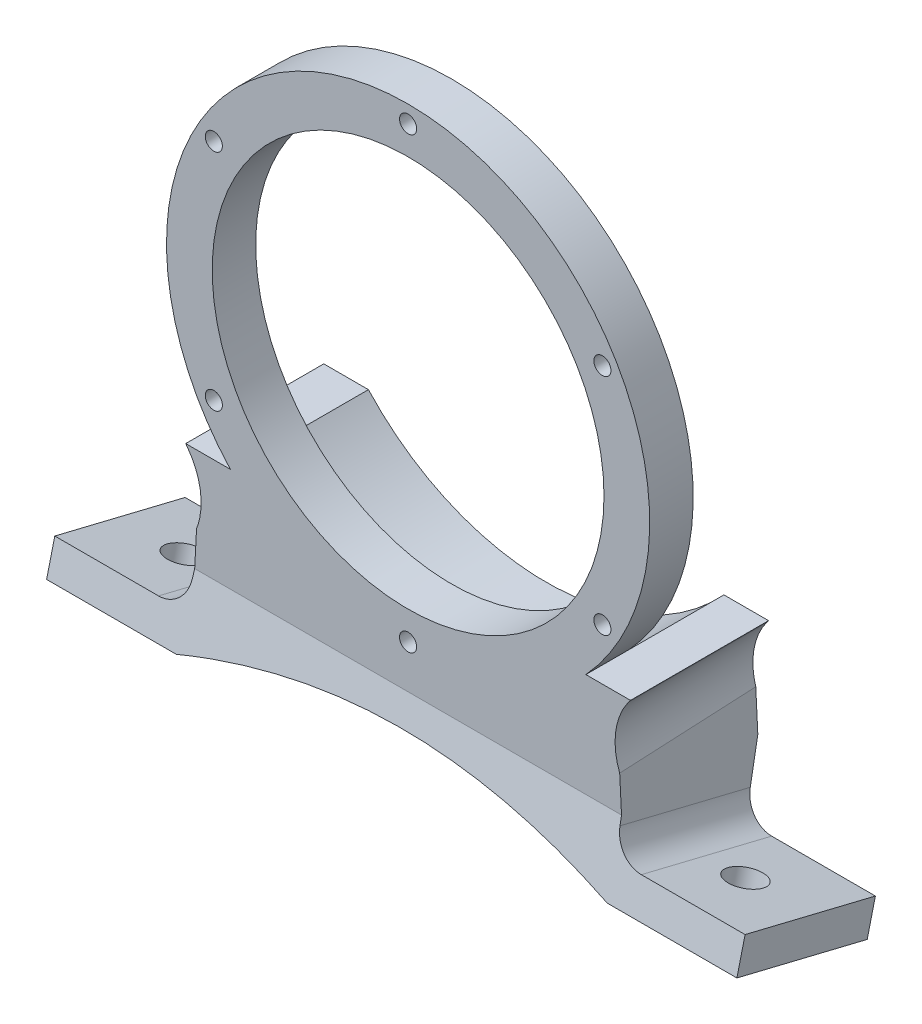
SolidWorks part; units mm, degrees
ref_plane "Front Plane" through (0, 0, 0) normal (0, 0, 1) x (1, 0, 0)
ref_plane "Top Plane" through (0, 0, 0) normal (0, 1, 0) x (1, 0, 0)
ref_plane "Right Plane" through (0, 0, 0) normal (1, 0, 0) x (0, 0, -1)
sketch "Sketch1" plane through (0, 0, 0) normal (0, 0, 1) x (1, 0, 0)
  circle A0 centre (0, 0) radius 44.45
  circle A1 centre (35.7452, -20.6375) radius 1.575
  circle A2 centre (0, 0) radius 44.45
  circle A3 centre (0, -41.275) radius 1.575
  circle A4 centre (0, 0) radius 44.45
  circle A5 centre (-35.7452, -20.6375) radius 1.575
  circle A6 centre (0, 0) radius 44.45
  circle A7 centre (-35.7452, 20.6375) radius 1.575
  circle A8 centre (0, 0) radius 44.45
  circle A9 centre (0, 41.275) radius 1.575
  circle A10 centre (0, 0) radius 44.45
  circle A11 centre (35.7452, 20.6375) radius 1.575
  circle A12 centre (0, 0) radius 36.0426
  point P24 (0, 0)
  dimension "D1" = 3.15
  dimension "D2" = 6
extrude "Boss-Extrude1" add sketch "Sketch1" along normal blind 8 contours A0 A12 A11 A9 A7 A5 A3 A1 region at (-43.1928, 0, 0)
sketch "Sketch4" plane through (0, 0, 8) normal (0, 0, 1) x (1, 0, 0)
  line L0 (-63.5, -44.45) -> (-39.6557, -44.45)
  line L1 (63.5, -44.45) -> (63.5, -49.2125)
  line L2 (63.5, -49.2125) -> (-63.5, -49.2125)
  line L3 (-63.5, -49.2125) -> (-63.5, -44.45)
  line L4 (-40.9153, -30.1094) -> (-32.699, -30.1094)
  line L5 (32.699, -30.1094) -> (40.9153, -30.1094)
  line L6 (39.6557, -44.45) -> (63.5, -44.45)
  line L7 (-36.0507, -35.7909) -> (-39.6557, -44.45)
  line L8 (36.0507, -35.7909) -> (39.6557, -44.45)
  circle A0 centre (0, 0) radius 44.45
  circle A1 centre (0, 0) radius 44.45 construction
  arc A2 (-40.9153, -30.1094) -> (-36.0507, -35.7909) centre (0, 0) ccw
  arc A3 (36.0507, -35.7909) -> (40.9153, -30.1094) centre (0, 0) ccw
  point P17 (24.5934, -44.45)
  circle M11 centre (0, 0) radius 44.45
  dimension "D2" = 127
  dimension "D3" = 6.35
  dimension "D1" = 4.7625
extrude "Boss-Extrude2" add sketch "Sketch4" against normal blind 25.4 contours A2 L7 L0 L3 L2 L1 L6 L8 A3 L5 L4 M11 region at (-51.5779, -45.7343, 8)
ref_plane "Plane1" through (0, -48.2929, 11.7725) normal (0, -0.9715, 0.2368) x (-1, 0, 0)
ref_axis "Axis1" through (0, 0, 8) along (0, 0, -1)
sketch "Sketch5" plane through (0, -48.2929, 11.7725) normal (0, -0.9715, 0.2368) x (-1, 0, 0)
  line L1 (-63.5, 28.5604) -> (63.5, 28.5604)
  line L2 (-63.5, 28.5604) -> (-63.5, 3.883)
  line L3 (-63.5, 3.883) -> (63.5, 3.883)
  line L4 (63.5, 28.5604) -> (63.5, 3.883)
extrude "Boss-Extrude3" add sketch "Sketch5" along normal blind 12.7 and the other way up to surface other way up to face at (0, -49.2125, -4.7)
sketch "Sketch6" plane through (0, -0.9196, -3.7725) normal (0, 0.2368, 0.9715) x (1, 0, 0)
  line L0 (63.5, -62.4071) -> (-63.5, -62.4071) construction
  line L1 (-39.6557, -62.4071) -> (-39.6557, -69.7981)
  line L2 (-39.6557, -69.7981) -> (39.6557, -69.7981)
  line L3 (39.6557, -69.7981) -> (39.6557, -62.4071)
  spline S0 degree 2 poles (-39.6557, -62.4071) (0, -47.6334) (39.6557, -62.4071) knots 0 0 0 1 1 1
  point P2 (-39.6557, -45.0801)
  point P4 (39.6557, -45.0801)
extrude "Cut-Extrude1" cut sketch "Sketch6" against normal through all
sketch "Sketch7" plane through (0, -60.6315, 14.7804) normal (0, -0.9715, 0.2368) x (1, 0, 0)
  line L0 (-63.5, -3.883) -> (-63.5, -28.5604) construction
  line L1 (-39.6557, -3.883) -> (-63.5, -3.883) construction
  line L2 (0, 0) -> (0, -35.7035) construction
  line L3 (0, 7.7724) -> (0, 0) construction
  circle A0 centre (-51.5779, -16.2217) radius 3.2639
  circle A1 centre (51.5779, -16.2217) radius 3.2639
  point P4 (-63.5, -16.2217)
  point P7 (-51.5779, -3.883)
  dimension "D1" = 6.5278
extrude "Cut-Extrude2" cut sketch "Sketch7" against normal through all
sketch "Sketch8" plane through (0, -6.7642, -27.7478) normal (0, -0.2368, -0.9715) x (-1, 0, 0)
  line L0 (-39.5977, -37.8778) -> (-39.5977, -56.0571)
  line L1 (-39.5977, -56.0571) -> (-63.5, -56.0571)
  line L3 (-63.5, -56.0571) -> (-63.5, -37.8778)
  line L4 (-63.5, -37.8778) -> (-39.5977, -37.8778)
  line L6 (-39.6557, -62.4071) -> (-63.5, -62.4071) construction
  line L7 (0, 0) -> (0, -27.5431) construction
  line L8 (0, -1.8947) -> (0, 0) construction
  line L9 (39.5977, -37.8778) -> (39.5977, -56.0571)
  line L10 (39.5977, -56.0571) -> (63.5, -56.0571)
  line L11 (63.5, -56.0571) -> (63.5, -37.8778)
  line L12 (63.5, -37.8778) -> (39.5977, -37.8778)
  dimension "D1" = 6.35
extrude "Cut-Extrude3" cut sketch "Sketch8" against normal through all
sketch "Sketch10" plane through (0, -6.7642, -27.7478) normal (0, -0.2368, -0.9715) x (-1, 0, 0)
  line L0 (-38.5619, -36.5118) -> (-39.5977, -56.0571)
  line L1 (-39.5977, -56.0571) -> (-58.3294, -36.5118)
  line L2 (-58.3294, -36.5118) -> (-38.5619, -36.5118)
  line L3 (0, 0) -> (0, -64.3842) construction
  line L4 (38.5619, -36.5118) -> (39.5977, -56.0571)
  line L5 (39.5977, -56.0571) -> (58.3294, -36.5118)
  line L6 (58.3294, -36.5118) -> (38.5619, -36.5118)
  line L7 (-36.0507, -30.6516) -> (-39.5977, -38.9289) construction
extrude "Cut-Extrude5" cut sketch "Sketch10" against normal through all
fillet "Fillet1" radius 5.08 2 edges at (-39.5977, -58.3041, -2.4837) (39.5977, -58.3041, -2.4837)
fillet "Fillet3" radius 12.7 2 edges at (-36.0507, -35.7909, -4.7) (36.0507, -35.7909, -4.7)
